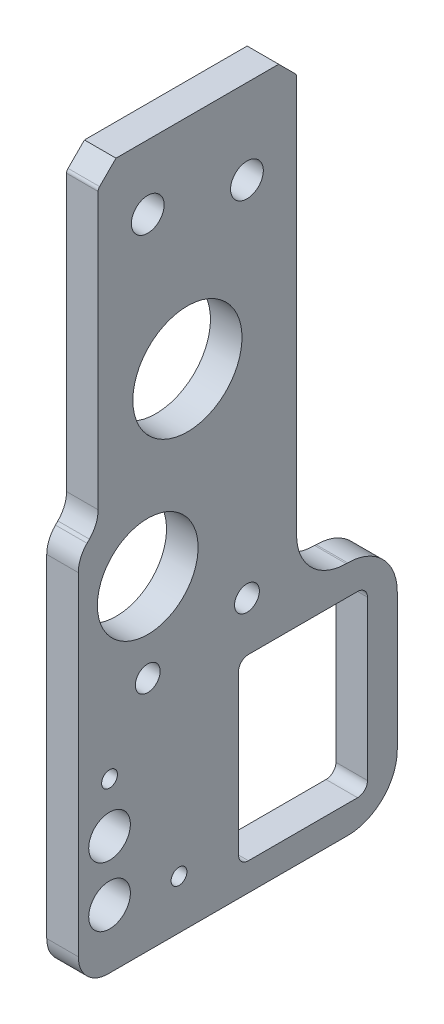
SolidWorks part; units mm, degrees
material "6061 Alloy"
ref_plane "Front Plane" through (0, 0, 0) normal (0, 0, 1) x (1, 0, 0)
ref_plane "Top Plane" through (0, 0, 0) normal (0, 1, 0) x (1, 0, 0)
ref_plane "Right Plane" through (0, 0, 0) normal (1, 0, 0) x (0, 0, -1)
sketch "Sketch1" plane through (0, 0, 0) normal (1, 0, 0) x (0, 0, -1)
  line L2 (0, 0) -> (0, 37.775)
  line L3 (0, 37.775) -> (2, 39.775)
  line L4 (2, 39.775) -> (2, 70.81)
  line L5 (2, 70.81) -> (22, 70.81)
  line L14 (-6.9356, -2) -> (62.4069, -2) construction
  line L15 (7, 37.775) -> (0, 37.775) construction
  line L23 (22, 70.81) -> (22, 23.81)
  line L31 (22, 23.81) -> (32.15, 23.81)
  line L32 (32.15, 23.81) -> (32.15, 0)
  line L33 (32.15, 0) -> (0, 0)
  line L35 (22.65, 20.81) -> (22.65, 2.81) construction
  line L36 (16.15, 20.81) -> (29.15, 20.81)
  line L37 (16.15, 20.81) -> (16.15, 2.81)
  line L38 (16.15, 2.81) -> (29.15, 2.81)
  line L39 (29.15, 20.81) -> (29.15, 2.81)
  circle A0 centre (7, 32.7) radius 5.075
  circle A1 centre (7, 64.31) radius 1.65
  circle A2 centre (17, 62.31) radius 1.65
  circle A5 centre (3.15, 5.95) radius 2.1
  circle A6 centre (3.15, 11.95) radius 2.1
  circle A9 centre (10.15, 4.95) radius 0.8
  circle A10 centre (3.15, 16.95) radius 0.8
  point P1 (7, 23.81)
  point P2 (17, 25.81)
  dimension "D11" = 10.15
  dimension "D13" = 3.3
  dimension "D17" = 15
  dimension "D21" = 2
  dimension "D33" = 4.2
  dimension "D36" = 1.6
  dimension "D4" = 18
  dimension "D5" = 13
  dimension "D22" = 15.75
  dimension "D6" = 16.15
  dimension "D7" = 5
  dimension "D8" = 2
  dimension "D9" = 2
  dimension "D10" = 47
  dimension "D12" = 34.7
  dimension "D14" = 8.5
  dimension "D15" = 6.5
  dimension "D16" = 5
  dimension "D18" = 38.11
  dimension "D19" = 3
  dimension "D20" = 3
  dimension "D23" = 7
  dimension "D24" = 20
  dimension "D25" = 5
  dimension "D28" = 2
  dimension "D30" = 6
  dimension "D32" = 3.15
  dimension "D38" = 12
extrude "Boss-Extrude1" add sketch "Sketch1" along normal blind 3.18
sketch "Sketch3" plane through (0, 0, 0) normal (-1, 0, 0) x (0, 0, 1)
  line L4 (-2, 70.81) -> (-2, 39.775) construction
  circle A0 centre (-11, 48.8109) radius 5.5
  circle A6 centre (-7, 32.7) radius 5.075 construction
  dimension "D1" = 11
  dimension "D3" = 16.6
  dimension "D2" = 9
extrude "Cut-Extrude4" cut sketch "Sketch3" against normal through all
sketch "Sketch8" [suppressed] plane through (3.18, 0, 0) normal (1, 0, 0) x (0, 0, -1)
  line L0 (2, 70.81) -> (2, 39.775) construction
  line L1 (11, 48.8109) -> (2, 48.8109) construction
  line L2 (2, 52.8109) -> (3.5, 52.8109)
  line L3 (3.5, 44.8109) -> (2, 44.8109)
  line L4 (2, 44.8109) -> (2, 52.8109)
  arc A0 (3.5, 44.8109) -> (3.5, 52.8109) centre (11, 48.8109) ccw
  circle A1 centre (7, 32.7) radius 5.075 construction
  point P11 (2, 48.8109)
  dimension "D1" = 16.6
  dimension "D2" = 17
  dimension "D3" = 9
  dimension "D4" = 8
extrude "Cut-Extrude5" [suppressed] cut sketch "Sketch8" against normal through all
fillet "Fillet2" radius 3 3 edges at (1.59, 37.775, 0) (1.59, 39.775, -2) (1.59, 0, 0)
fillet "Chamfer2" radius 1.8 2 edges at (1.59, 70.81, -22) (1.59, 70.81, -2) profile chamfer
fillet "Fillet4" radius 0.5 2 edges at (1.59, 69.01, -2) (1.59, 69.01, -22)
fillet "Fillet5" [suppressed] radius 0.3
sketch "BallRef" plane through (0, 0, 0) normal (-1, 0, 0) x (0, 0, 1)
  line L0 (-31.524, -10.56) -> (65.6624, -10.56) construction
  line L1 (-0.75, 32.7) -> (-0.75, 29.3885) construction
  line L2 (-0.75, 29.3885) -> (31.3703, 29.3885) construction
  line L3 (31.3703, 10.85) -> (31.3703, 29.3885) construction
  line L4 (1.092, -10.56) -> (-13.908, 4.44) construction
  line L5 (-13.908, 4.44) -> (-13.908, -10.56) construction
  line L6 (-13.908, -10.56) -> (1.092, -10.56) construction
  circle A0 centre (-7, 32.7) radius 6.25 construction
  circle A1 centre (9.9603, 10.85) radius 21.41 construction
  dimension "D1" = 12.5
  dimension "D2" = 42.82
  dimension "D3" = 43.26
  dimension "D4" = 45
  dimension "D5" = 15
hole_wizard "M2 Tapped Hole1" positions "3DSketch1" profile "Sketch12" tap size "M2" standard "AS" end condition through all
sketch3d "3DSketch1"
  line L0 (3.18, 16.95, -3.15) -> (0, 16.95, -3.15) construction
  line L1 (3.18, 4.95, -10.15) -> (0, 4.95, -10.15) construction
  point P0 (0, 16.95, -3.15)
  point P4 (0, 4.95, -10.15)
sketch "Sketch12" plane through (0, 16.95, -3.15) normal (0, 1, 0) x (0, 0, 1)
  line L0 (0, 0) -> (0, 3.18)
  line L1 (0, 3.18) -> (0.8, 3.18)
  line L2 (0.8, 3.18) -> (0.8, 0)
  line L5 (0.8, 0) -> (0, 0)
  line L11 (0, -6.35) -> (0, 107.95) construction
  dimension "Thru Tap Drill Dia." = 1.6
  dimension "Thru Tap Drill Depth" = 3.18
cosmetic thread "Hole Thread3" parameters "D2"=2
cosmetic thread "Hole Thread4" parameters "D2"=2
fillet "Fillet9" radius 1 4 edges at (1.59, 2.81, -29.15) (1.59, 2.81, -16.15) (1.59, 20.81, -29.15) (1.59, 20.81, -16.15)
fillet "Fillet11" radius 5 3 edges at (1.59, 0, -32.15) (1.59, 23.81, -22) (1.59, 23.81, -32.15)
hole_wizard "M3x0.5 Tapped Hole1" positions "Sketch13" profile "Sketch14" tap size "M3x0.5" standard "ANSI Metric" end condition through all
sketch "Sketch13" plane through (3.18, 0, 0) normal (1, 0, 0) x (0, 0, -1)
  point P0 (7, 23.81)
  point P3 (17, 25.81)
cosmetic thread "Hole Thread5" parameters "D2"=3
cosmetic thread "Hole Thread6" parameters "D2"=3
sketch "Sketch14" plane through (3.18, 23.81, -7) normal (0, 1, 0) x (0, 0, -1)
  line L0 (0, 0) -> (0, 3.18)
  line L1 (0, 3.18) -> (1.25, 3.18)
  line L2 (1.25, 3.18) -> (1.25, 0)
  line L5 (1.25, 0) -> (0, 0)
  line L11 (0, -6.35) -> (0, 107.95) construction
  dimension "Thru Tap Drill Dia." = 2.5
  dimension "Thru Tap Drill Depth" = 3.18
equation "\"7.5.00mm\"=5"
